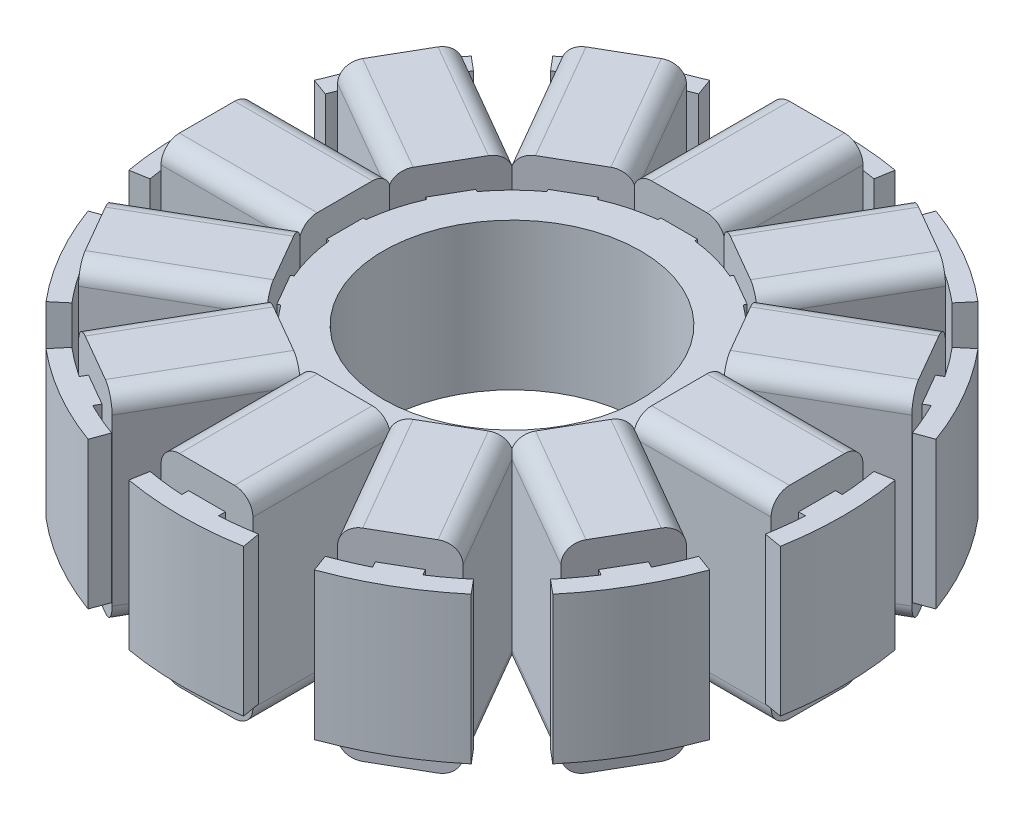
SolidWorks part; units mm, degrees
ref_plane "Front Plane" through (0, 0, 0) normal (0, 0, 1) x (1, 0, 0)
ref_plane "Top Plane" through (0, 0, 0) normal (0, 1, 0) x (1, 0, 0)
ref_plane "Right Plane" through (0, 0, 0) normal (1, 0, 0) x (0, 0, -1)
sketch "Sketch1" plane through (0, 0, 0) normal (0, 1, 0) x (1, 0, 0)
  line L0 (-1, 8.9443) -> (-1, 16.9706)
  line L1 (0, 0) -> (0, 13.6776) construction
  line L2 (1, 8.9443) -> (1, 16.9706)
  line L3 (-3.1257, 17.7265) -> (-2.952, 16.7417)
  line L4 (3.1257, 17.7265) -> (2.952, 16.7417)
  circle A0 centre (0, 0) radius 7
  circle A1 centre (0, 0) radius 9
  arc A2 (2.952, 16.7417) -> (1, 16.9706) centre (0, 0) ccw
  arc A3 (3.1257, 17.7265) -> (-3.1257, 17.7265) centre (0, 0) ccw
  arc A4 (-1, 16.9706) -> (-2.952, 16.7417) centre (0, 0) ccw
  dimension "D1" = 14
  dimension "D2" = 2
  dimension "D3" = 36
  dimension "D4" = 1
  dimension "D5" = 20
  dimension "D6" = 2
extrude "Boss-Extrude1" add sketch "Sketch1" along normal blind 8 contours A0 A1 region at (0, 0, -8.7454)
extrude "Boss-Extrude4" add sketch "Sketch1<3>" along normal blind 8 contours A4 L0 A1 L2 A2 L4 A3 L3 region at (0, 0, -14.2089)
sketch "Sketch1<3>" plane through (0, 0, 0) normal (0, 1, 0) x (1, 0, 0) same geometry as "Sketch1"
ref_plane "Plane1" through (0, 0, -9.1) normal (0, 0, 1) x (1, 0, 0)
sketch "Sketch2" plane through (0, 0, -9.1) normal (0, 0, 1) x (1, 0, 0)
  line L3 (1, 8) -> (-1, 8)
  line L4 (-1, 8) -> (-1, 0)
  line L5 (-1, 8) -> (-1, 0)
  line L8 (-2.5, 8.5) -> (-2.5, -0.5)
  line L9 (1.5, -1.5) -> (-1.5, -1.5)
  line L10 (2.5, 8.5) -> (2.5, -0.5)
  line L11 (1.5, 9.5) -> (-1.5, 9.5)
  line L15 (1, 8) -> (-1, 8)
  line L36 (1, 0) -> (-1, 0)
  line L41 (1, 0) -> (-1, 0)
  line L44 (1, 8) -> (1, 0)
  line L45 (1, 8) -> (1, 0)
  arc A0 (-2.5, -0.5) -> (-1.5, -1.5) centre (-1.5, -0.5) ccw
  arc A1 (1.5, -1.5) -> (2.5, -0.5) centre (1.5, -0.5) ccw
  arc A2 (2.5, 8.5) -> (1.5, 9.5) centre (1.5, 8.5) ccw
  arc A3 (-2.5, 8.5) -> (-1.5, 9.5) centre (-1.5, 8.5) cw
  dimension "D2" = 1
  dimension "D1" = 1.5
  dimension "D3" = 1.5
  dimension "D4" = 1.5
  dimension "D5" = 1.5
extrude "Boss-Extrude5" add sketch "Sketch2" against normal blind 7.5 contours A2 L11 A3 L8 A0 L9 A1 L10
pattern_circular "CirPattern2" count 12 over 360 about axis through (0, 8, 0) along (0, -1, 0) of "Boss-Extrude4"
pattern_circular "CirPattern3" count 12 over 360 of "Boss-Extrude5"
